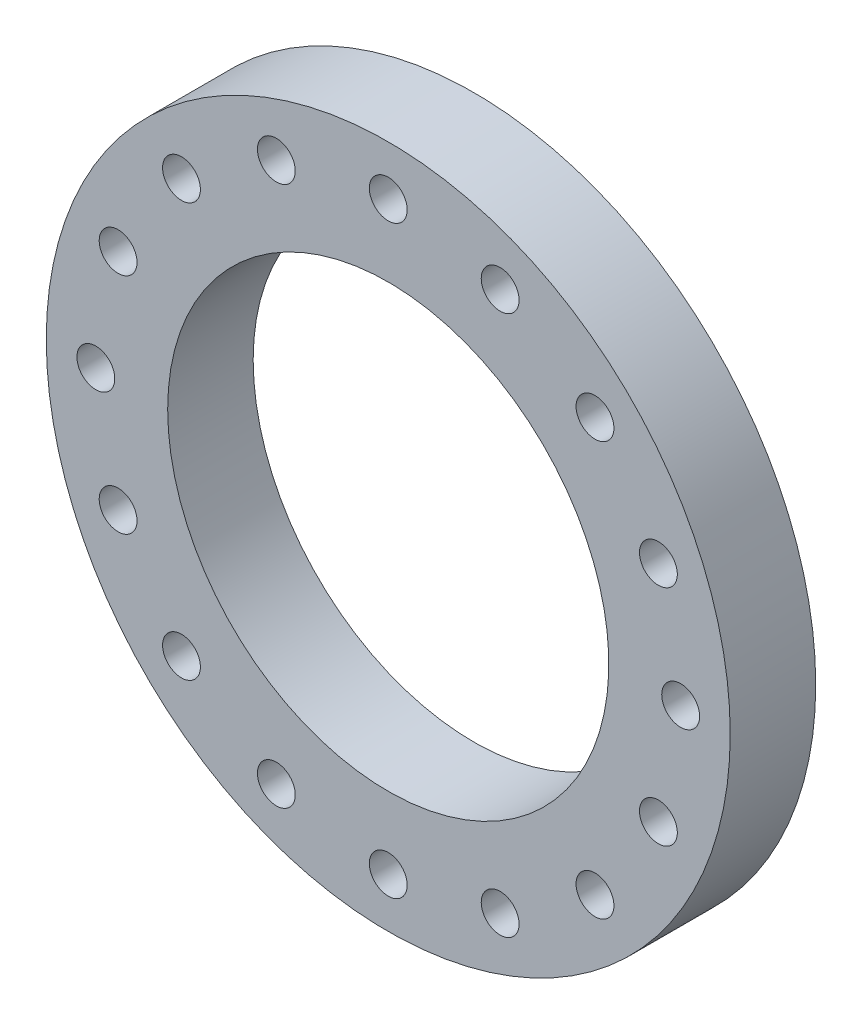
SolidWorks part; units mm, degrees
ref_plane "Front Plane" through (0, 0, 0) normal (0, 0, 1) x (1, 0, 0)
ref_plane "Top Plane" through (0, 0, 0) normal (0, 1, 0) x (1, 0, 0)
ref_plane "Right Plane" through (0, 0, 0) normal (1, 0, 0) x (0, 0, -1)
sketch "Sketch1" plane through (0, 0, 0) normal (0, 0, 1) x (1, 0, 0)
  circle A0 centre (0, 0) radius 76.2
extrude "Extrude-Thin1" add sketch "Sketch1" along normal blind 19.05 thin thin type one direction reverse wall 27.051
sketch "Sketch2" plane through (0, 0, 0) normal (0, 0, 1) x (1, 0, 0)
  circle A0 centre (0, 65.151) radius 4.2164
  dimension "D2" = 8.4328
  dimension "D1" = 65.151
extrude "Cut-Extrude3" cut sketch "Sketch2" along normal through all
ref_axis "Axis1" through (0, 0, 78.236) along (0, 0, -1)
pattern_circular "CirPattern1" count 16 over 360 about axis through (0, 0, 78.236) along (0, 0, -1) of "Cut-Extrude3"
sketch "Sketch3" plane through (0, 0, 0) normal (0, 0, 1) x (1, 0, 0)
  line L0 (0, 0) -> (44.4565, 0)
